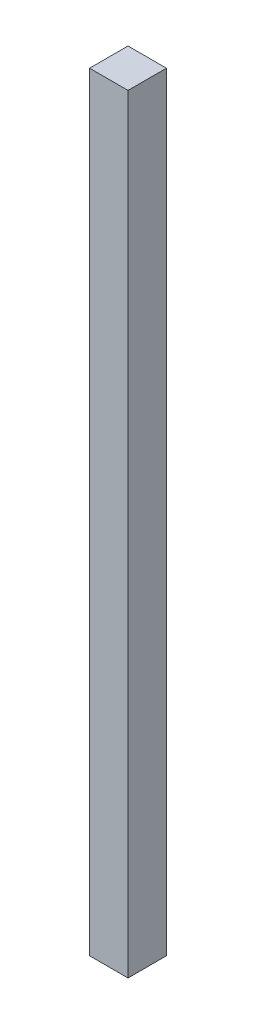
SolidWorks part; units mm, degrees
ref_plane "前视基准面" through (0, 0, 0) normal (0, 0, 1) x (1, 0, 0)
ref_plane "上视基准面" through (0, 0, 0) normal (0, 1, 0) x (1, 0, 0)
ref_plane "右视基准面" through (0, 0, 0) normal (1, 0, 0) x (0, 0, -1)
other "Configuration Table"
sketch "草图1" plane through (0, 0, 0) normal (0, 1, 0) x (1, 0, 0)
  line L1 (-10, -10) -> (10, -10)
  line L2 (-10, -10) -> (-10, 10)
  line L3 (-10, 10) -> (10, 10)
  line L4 (10, -10) -> (10, 10)
  line L5 (-10, -10) -> (10, 10) construction
  line L6 (-10, 10) -> (10, -10) construction
  point P0 (0, 0)
  dimension "D1" = 20
  dimension "D2" = 20
extrude "凸台-拉伸1" add sketch "草图1" along normal blind 200 and the other way blind 200
